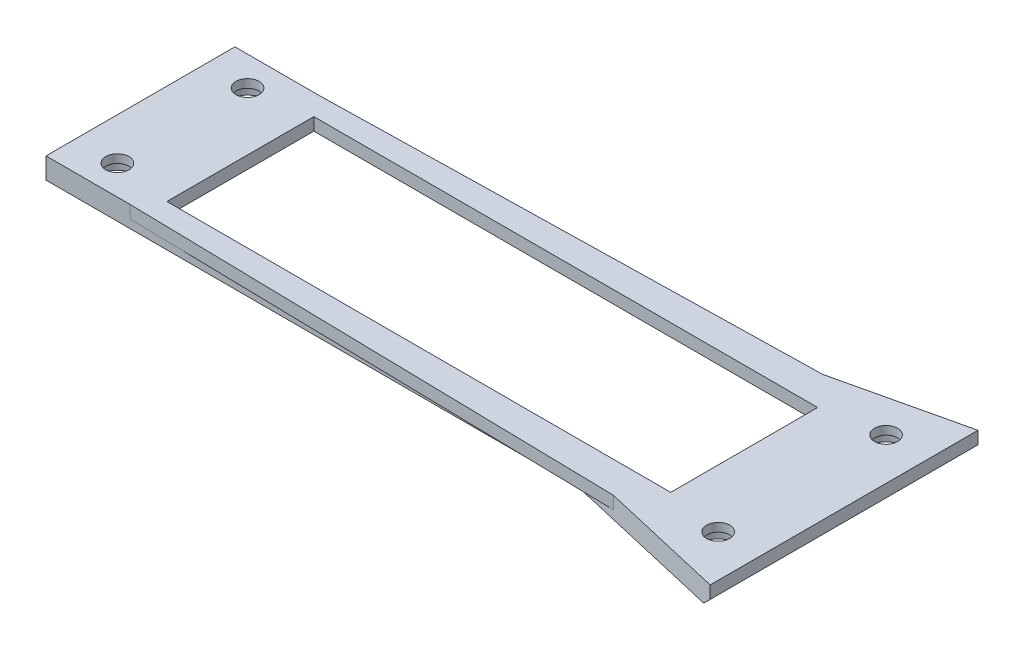
SolidWorks part; units mm, degrees
ref_plane "Front Plane" through (0, 0, 0) normal (0, 0, 1) x (1, 0, 0)
ref_plane "Top Plane" through (0, 0, 0) normal (0, 1, 0) x (1, 0, 0)
ref_plane "Right Plane" through (0, 0, 0) normal (1, 0, 0) x (0, 0, -1)
sketch "Sketch1" plane through (0, 0, 0) normal (0, 1, 0) x (1, 0, 0)
  line L0 (-73.8, 35.6771) -> (-83.8, 35.6771)
  line L1 (-73.8, 35.6771) -> (73.8, 35.6771)
  line L3 (-73.8, -35.6771) -> (73.8, -35.6771)
  line L5 (-83.8, 0) -> (83.8, 0) construction
  line L7 (-83.8, 35.6771) -> (-83.8, -35.6771)
  line L8 (-83.8, -35.6771) -> (-73.8, -35.6771)
  line L10 (73.8, -35.6771) -> (83.8, -35.6771)
  line L11 (83.8, -35.6771) -> (83.8, 35.6771)
  line L12 (83.8, 35.6771) -> (73.8, 35.6771)
  point P0 (0, 0)
  dimension "D1" = 147.6
  dimension "D2" = 10
extrude "Boss-Extrude1" add sketch "Sketch1" along normal blind 5
sketch "Sketch2" plane through (0, 5, 0) normal (0, 1, 0) x (1, 0, 0)
  circle A0 centre (-73.8, -15.5) radius 2.75
  circle A1 centre (-73.8, 15.5) radius 2.75
  circle A2 centre (73.7972, -20) radius 2.75
  circle A3 centre (73.7972, 20) radius 2.75
  dimension "D1" = 5.5
extrude "Cut-Extrude1" cut sketch "Sketch2" against normal through all both and the other way through all
sketch "Sketch3" plane through (0, 5, 0) normal (0, 1, 0) x (1, 0, 0)
  line L0 (-63.8, -22.5) -> (53.7544, -24.9303)
  line L1 (53.7544, -24.9303) -> (90.0899, -33.3544)
  line L2 (118.7544, -40) -> (53.7544, -24.9303) construction
  line L3 (90.0899, -33.3544) -> (45.1068, -114.5197)
  line L4 (45.1068, -114.5197) -> (-93.8089, -48.4817)
  line L5 (-93.8089, -48.4817) -> (-93.8089, -22.5)
  line L6 (-63.8, -22.5) -> (-159.8, -22.5) construction
  line L7 (-93.8089, -22.5) -> (-63.8, -22.5)
  line L8 (53.7544, 24.9303) -> (-63.8, 22.5)
  line L9 (-63.8, 22.5) -> (-93.8089, 22.5)
  line L10 (-63.8, 22.5) -> (-159.8, 22.5) construction
  line L11 (-93.8089, 22.5) -> (-93.8089, 75.1037)
  line L12 (-93.8089, 75.1037) -> (90.0899, 109.5378)
  line L13 (90.0899, 109.5378) -> (90.0899, 33.3544)
  line L14 (53.7544, 24.9303) -> (118.7544, 40) construction
  line L15 (90.0899, 33.3544) -> (53.7544, 24.9303)
extrude "Cut-Extrude2" cut sketch "Sketch3" against normal through all both and the other way through all
chamfer "Chamfer3" distance 2 angle 45 3 edges at (83.8, 0, 0) (-5.0228, 0, -23.7151) (-5.0228, 0, 23.7151)
sketch "Sketch4" plane through (0, 0, 0) normal (0, -1, 0) x (1, 0, 0)
  line L1 (60, 17.5) -> (-60, 17.5)
  line L2 (60, 17.5) -> (60, -17.5)
  line L3 (60, -17.5) -> (-60, -17.5)
  line L4 (-60, 17.5) -> (-60, -17.5)
  line L5 (60, 17.5) -> (-60, -17.5) construction
  line L6 (60, -17.5) -> (-60, 17.5) construction
  point P0 (0, 0)
  dimension "D1" = 120
  dimension "D2" = 35
extrude "Cut-Extrude3" cut sketch "Sketch4" against normal through all both and the other way through all
chamfer "Chamfer4" distance 2 angle 45 4 edges at (60, 0, 0) (0, 0, 17.5) (-60, 0, 0) (0, 0, -17.5)
sketch "Sketch5" plane through (0, 0, 0) normal (0, -1, 0) x (1, 0, 0)
  circle A0 centre (-73.8, 15.5) radius 5
  circle A1 centre (-73.8, -15.5) radius 5
  circle A2 centre (73.7972, 20) radius 5
  circle A3 centre (73.7972, -20) radius 5
  dimension "D1" = 10
extrude "Cut-Extrude4" cut sketch "Sketch5" against normal offset from surface (3 mm away) 2 up to face at (0, 5, 0)
